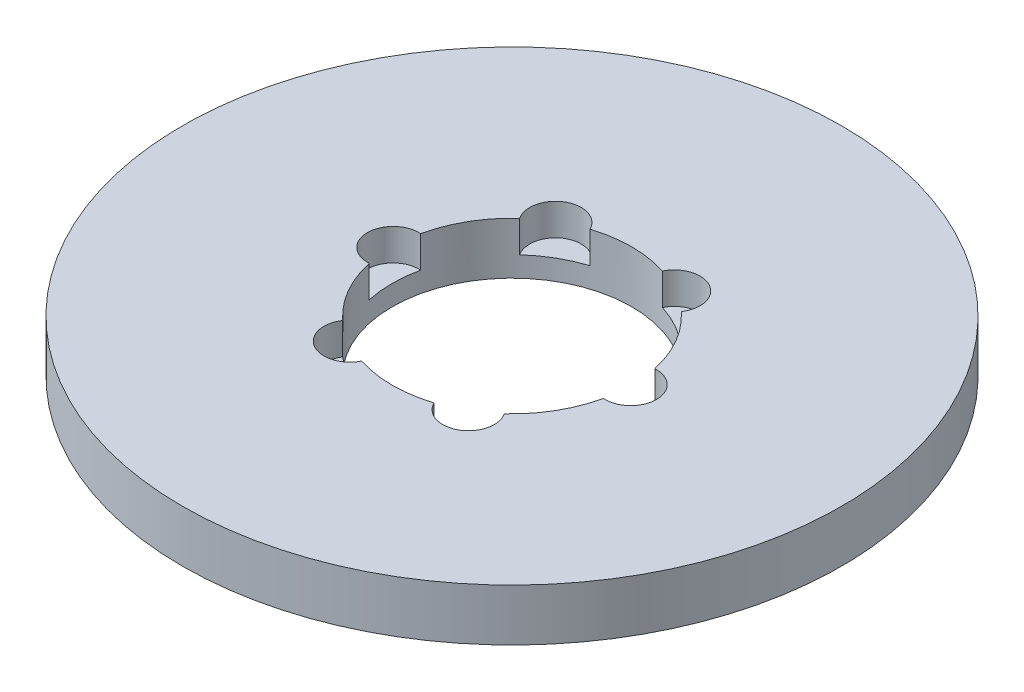
SolidWorks part; units mm, degrees
ref_plane "Front Plane" through (0, 0, 0) normal (0, 0, 1) x (1, 0, 0)
ref_plane "Top Plane" through (0, 0, 0) normal (0, 1, 0) x (1, 0, 0)
ref_plane "Right Plane" through (0, 0, 0) normal (1, 0, 0) x (0, 0, -1)
sketch "Sketch1" plane through (0, 0, 0) normal (0, 1, 0) x (1, 0, 0)
  circle A0 centre (0, 0) radius 82.5
  dimension "FLANGE_OD" = 165
extrude "Boss-Extrude1" add sketch "Sketch1" along normal blind 13
sketch "Sketch2" plane through (0, 0, 0) normal (0, 1, 0) x (1, 0, 0)
  circle A0 centre (0, 0) radius 30
  dimension "BORE_D" = 60
extrude "Cut-Extrude1" cut sketch "Sketch2" along normal through all
sketch "Sketch3" plane through (0, 13, 0) normal (0, 1, 0) x (1, 0, 0)
  circle A0 centre (0, 0) radius 29.7383 construction
  circle A1 centre (-29.7383, 0) radius 6.4517
  dimension "BOLT_D" = 12.9034
  dimension "BOLT_PCD" = 59.4767
extrude "Cut-Extrude2" cut sketch "Sketch3" against normal blind 7.9217
pattern_circular "CirPattern1" count 6 over 360 about axis through (0, 0, 0) along (0, 1, 0) of "Cut-Extrude2"
